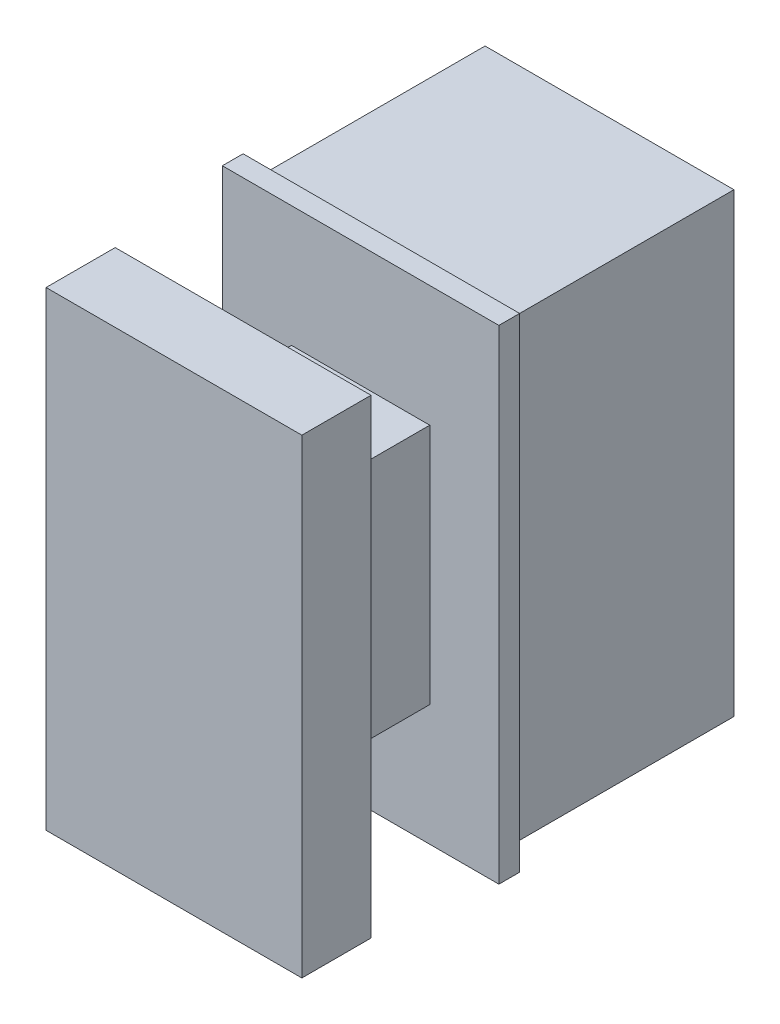
SolidWorks part; units mm, degrees
ref_plane "Piano frontale" through (0, 0, 0) normal (0, 0, 1) x (1, 0, 0)
ref_plane "Piano superiore" through (0, 0, 0) normal (0, 1, 0) x (1, 0, 0)
ref_plane "Piano destro" through (0, 0, 0) normal (1, 0, 0) x (0, 0, -1)
sketch "Schizzo1" plane through (0, 0, 0) normal (0, 0, 1) x (1, 0, 0)
  line L5 (0, 0) -> (4, 0)
  line L6 (0, 0) -> (0, 7)
  line L7 (0, 7) -> (4, 7)
  line L8 (4, 0) -> (4, 7)
  dimension "D1" = 4
  dimension "D2" = 7
extrude "Estrusione-Estrusione1" add sketch "Schizzo1" along normal blind 0.3
sketch "Schizzo2" plane through (0, 0, 0) normal (0, 0, 1) x (1, 0, 0)
  line L0 (0, 0) -> (4, 0) construction
  line L1 (0.2, 6.8) -> (3.8, 6.8)
  line L2 (0.2, 6.8) -> (0.2, 0.2)
  line L3 (0.2, 0.2) -> (3.8, 0.2)
  line L4 (3.8, 6.8) -> (3.8, 0.2)
  line L5 (4, 0) -> (4, 7) construction
  line L6 (4, 7) -> (0, 7) construction
  line L7 (0, 7) -> (0, 0) construction
  line L8 (0, 0) -> (4, 0)
  line L9 (4, 0) -> (4, 7)
  line L10 (4, 7) -> (0, 7)
  line L11 (0, 7) -> (0, 0)
  dimension "D1" = 0.2
  dimension "D2" = 0.2
  dimension "D3" = 0.2
  dimension "D4" = 0.2
extrude "Estrusione-Estrusione2" add sketch "Schizzo2" against normal blind 3.3 contours L2 L1 L4 L3
sketch "Schizzo3" plane through (0, 0, 0) normal (0, 0, 1) x (1, 0, 0)
  line L0 (0.2, 6.8) -> (3.8, 6.8) construction
  line L1 (3.6, 6.6) -> (0.4, 6.6)
  line L2 (3.6, 6.6) -> (3.6, 0.4)
  line L3 (3.6, 0.4) -> (0.4, 0.4)
  line L4 (0.4, 6.6) -> (0.4, 0.4)
  line L5 (0.2, 0.2) -> (3.8, 0.2) construction
  line L6 (3.8, 6.8) -> (3.8, 0.2) construction
  line L7 (0.2, 6.8) -> (0.2, 0.2) construction
  dimension "D1" = 0.2
  dimension "D2" = 0.2
  dimension "D3" = 0.2
  dimension "D4" = 0.2
extrude "Taglio-Estrusione1" cut sketch "Schizzo3" against normal through all
sketch "Schizzo6" plane through (0, 0, 0) normal (0, 0, 1) x (1, 0, 0)
  line L0 (4, 3.5) -> (0, 3.5) construction
  line L1 (4, 0) -> (4, 7) construction
  line L2 (0, 7) -> (0, 0) construction
  line L3 (0, 3.5) -> (2, 3.5) construction
  line L4 (2, 3.5) -> (2, 0) construction
  line L5 (0, 0) -> (4, 0) construction
  line L6 (2, 3.5) -> (2, 7) construction
  line L7 (4, 7) -> (0, 7) construction
  line L13 (1, 1.75) -> (3, 1.75)
  line L14 (1, 1.75) -> (1, 5.25)
  line L15 (1, 5.25) -> (3, 5.25)
  line L16 (3, 1.75) -> (3, 5.25)
  line L17 (1, 1.75) -> (3, 5.25) construction
  line L18 (1, 5.25) -> (3, 1.75) construction
  dimension "D1" = 2
  dimension "D2" = 3.5
extrude "Estrusione-Estrusione3" add sketch "Schizzo6" along normal blind 2 contours L14 L13 L16 L15
sketch "Schizzo7" plane through (0, 0, 2) normal (0, 0, 1) x (1, 0, 0)
  line L0 (1, 5.25) -> (2, 5.25) construction
  line L1 (1, 5.25) -> (3, 5.25) construction
  line L2 (2, 5.25) -> (2, 1.75) construction
  line L3 (1, 1.75) -> (3, 1.75) construction
  line L4 (2, 1.75) -> (3, 1.75) construction
  line L5 (3, 1.75) -> (1, 5.25) construction
  line L6 (1, 5.25) -> (1, 1.75) construction
  line L7 (1, 1.75) -> (3, 5.25) construction
  line L9 (0.15, 6.9) -> (3.85, 6.9)
  line L10 (0.15, 6.9) -> (0.15, 0.1)
  line L11 (0.15, 0.1) -> (3.85, 0.1)
  line L12 (3.85, 6.9) -> (3.85, 0.1)
  line L13 (0.15, 6.9) -> (3.85, 0.1) construction
  line L14 (0.15, 0.1) -> (3.85, 6.9) construction
  point P13 (2, 3.5)
  dimension "D1" = 3.7
  dimension "D2" = 6.8
extrude "Estrusione-Estrusione4" add sketch "Schizzo7" along normal blind 1
